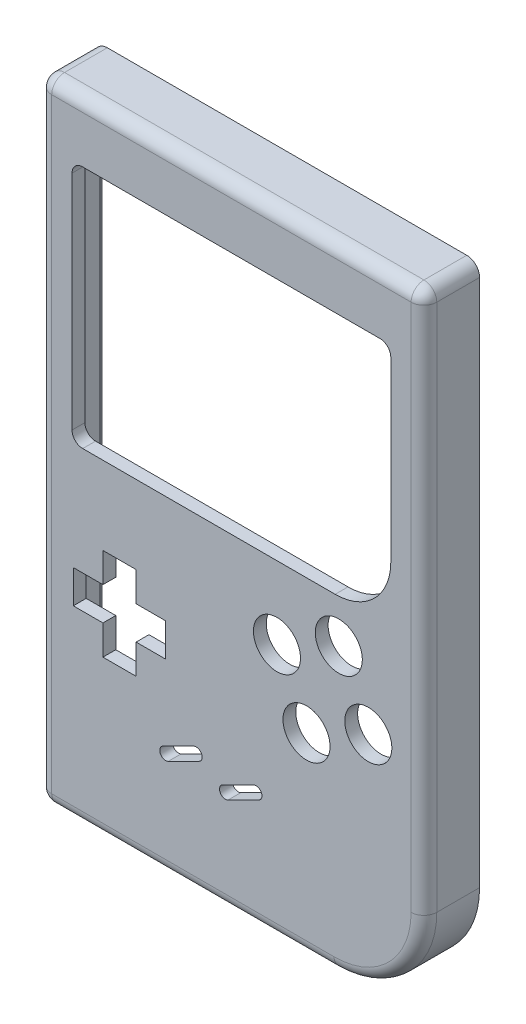
SolidWorks part; units mm, degrees
ref_plane "Front Plane" through (0, 0, 0) normal (0, 0, 1) x (1, 0, 0)
ref_plane "Top Plane" through (0, 0, 0) normal (0, 1, 0) x (1, 0, 0)
ref_plane "Right Plane" through (0, 0, 0) normal (1, 0, 0) x (0, 0, -1)
sketch "Sketch1" plane through (0, 0, 0) normal (0, 0, 1) x (1, 0, 0)
  line L1 (-45, -73.75) -> (45, -73.75)
  line L2 (-45, -73.75) -> (-45, 73.75)
  line L3 (-45, 73.75) -> (45, 73.75)
  line L4 (45, -73.75) -> (45, 73.75)
  line L5 (-45, -73.75) -> (45, 73.75) construction
  line L6 (-45, 73.75) -> (45, -73.75) construction
  point P0 (0, 0)
  dimension "D1" = 90
  dimension "D2" = 147.5
extrude "Boss-Extrude1" add sketch "Sketch1" along normal blind 13
fillet "Rounded Bottom Corner" radius 21 1 edges at (45, -73.75, 6.5)
fillet "Round Edges" radius 3 8 edges at (-10.5, -73.75, 13) (38.8492, -67.5992, 13) (-45, 0, 13) (45, 10.5, 13) (0, 73.75, 13) (-45, -73.75, 6.5) (-45, 73.75, 6.5) (45, 73.75, 6.5)
shell "Shell2" thickness 3 removed face at (-1.784, 1.784, 0)
sketch "Sketch2" plane through (0, 0, 13) normal (0, 0, 1) x (1, 0, 0)
  line L0 (45, 73.75) -> (-45, 73.75) construction
  line L1 (-34.75, 59.75) -> (34.75, 59.75)
  line L2 (-37.25, 57.25) -> (-37.25, 5.25)
  line L3 (-34.75, 2.75) -> (24.25, 2.75)
  line L4 (37.25, 57.25) -> (37.25, 15.75)
  line L6 (0, -7.15) -> (0, 7.15) construction
  arc A0 (-37.25, 5.25) -> (-34.75, 2.75) centre (-34.75, 5.25) ccw
  arc A1 (34.75, 59.75) -> (37.25, 57.25) centre (34.75, 57.25) cw
  arc A2 (-34.75, 59.75) -> (-37.25, 57.25) centre (-34.75, 57.25) ccw
  arc A3 (24.25, 2.75) -> (37.25, 15.75) centre (24.25, 15.75) ccw
  point P8 (0, 59.75)
  dimension "D4" = 2.5
  dimension "D5" = 13
  dimension "D1" = 14
  dimension "D2" = 74.5
  dimension "D3" = 57
extrude "Cut-Extrude1" cut sketch "Sketch2" against normal through all
sketch "Sketch3" plane through (0, 0, 0) normal (0, 0, -1) x (-1, 0, 0)
  line L0 (-42, -52.75) -> (-42, 70.75) construction
  line L1 (-42, 70.75) -> (42, 70.75) construction
  line L2 (42, -70.75) -> (42, 70.75) construction
  line L3 (-24, -70.75) -> (42, -70.75) construction
  line L4 (-42, -52.75) -> (-42, 70.75)
  line L5 (-42, 70.75) -> (42, 70.75)
  line L6 (42, -70.75) -> (42, 70.75)
  line L7 (-24, -70.75) -> (42, -70.75)
  line L8 (-43.25, -52.75) -> (-43.25, 72)
  line L9 (-43.25, 72) -> (43.25, 72)
  line L10 (43.25, -72) -> (43.25, 72)
  line L11 (-24, -72) -> (43.25, -72)
  arc A0 (-42, -52.75) -> (-24, -70.75) centre (-24, -52.75) ccw construction
  arc A1 (-42, -52.75) -> (-24, -70.75) centre (-24, -52.75) ccw
  arc A2 (-43.25, -52.75) -> (-24, -72) centre (-24, -52.75) ccw
  dimension "D1" = 1.25
extrude "Cut-Extrude2" cut sketch "Sketch3" against normal blind 1.75
sketch "Sketch4" plane through (0, -73.75, 0) normal (0, -1, 0) x (1, 0, 0)
  line L0 (-3.5, 0) -> (3.5, 0)
  line L1 (-42, 0) -> (24, 0) construction
  line L2 (-3.5, 0) -> (-3.5, 4)
  line L3 (3.5, 0) -> (3.5, 4)
  arc A0 (-3.5, 4) -> (3.5, 4) centre (0, 4) cw
  point P6 (0, 0)
  dimension "D1" = 7
  dimension "D2" = 4
extrude "Cut-Extrude3" cut sketch "Sketch4" against normal up to next
sketch "Sketch6" plane through (0, 0, 13) normal (0, 0, 1) x (1, 0, 0)
  line L0 (45, 70.75) -> (45, -52.75) construction
  line L1 (24, -73.75) -> (-42, -73.75) construction
  line L2 (17.5469, -28.66) -> (32, -21.75) construction
  line L3 (17.5469, -28.66) -> (10.6455, -14.2249) construction
  line L4 (32, -21.75) -> (25.0986, -7.3149) construction
  line L5 (10.6455, -14.2249) -> (25.0986, -7.3149) construction
  circle A0 centre (32, -21.75) radius 5.5
  circle A1 centre (17.5469, -28.66) radius 5.5
  circle A2 centre (25.0986, -7.3149) radius 5.5
  circle A3 centre (10.6455, -14.2249) radius 5.5
  dimension "D1" = 11
  dimension "D4" = 45.09
  dimension "D6" = 11
  dimension "D8" = 11
  dimension "D9" = 11
  dimension "D2" = 13
  dimension "D3" = 52
  dimension "D5" = 16.02
  dimension "D7" = 16
extrude "Cut-Extrude4" cut sketch "Sketch6" against normal through all
sketch "Sketch7" plane through (0, 0, 13) normal (0, 0, 1) x (1, 0, 0)
  line L0 (-45, -70.75) -> (-45, 70.75) construction
  line L1 (-29.525, -16.01) -> (-22.775, -16.01) construction
  line L2 (-36.45, -22.935) -> (-36.45, -29.685) construction
  line L3 (-29.525, -36.61) -> (-22.775, -36.61) construction
  line L4 (-15.85, -22.935) -> (-15.85, -29.685) construction
  line L5 (24, -73.75) -> (-42, -73.75) construction
  line L6 (-22.775, -16.01) -> (-29.525, -36.61) construction
  line L7 (-29.525, -16.01) -> (-22.775, -16.01)
  line L8 (-29.525, -16.01) -> (-29.525, -36.61) construction
  line L9 (-29.525, -36.61) -> (-22.775, -36.61)
  line L10 (-22.775, -16.01) -> (-22.775, -36.61) construction
  line L11 (-15.85, -29.685) -> (-36.45, -29.685) construction
  line L12 (-15.85, -29.685) -> (-15.85, -22.935)
  line L13 (-15.85, -22.935) -> (-36.45, -22.935) construction
  line L14 (-36.45, -29.685) -> (-36.45, -22.935)
  line L15 (-36.45, -29.685) -> (-15.85, -22.935) construction
  line L16 (-29.525, -16.01) -> (-22.775, -36.61) construction
  line L17 (-15.85, -29.685) -> (-36.45, -22.935) construction
  line L18 (-30.025, -15.51) -> (-22.275, -15.51)
  line L19 (-22.275, -15.51) -> (-22.275, -37.11)
  line L20 (-30.025, -37.11) -> (-22.275, -37.11)
  line L21 (-30.025, -15.51) -> (-30.025, -37.11)
  line L22 (-15.35, -22.435) -> (-36.95, -22.435)
  line L23 (-36.95, -22.435) -> (-36.95, -30.185)
  line L24 (-15.35, -30.185) -> (-36.95, -30.185)
  line L25 (-15.35, -22.435) -> (-15.35, -30.185)
  point P16 (-26.15, -26.31)
  point P17 (-26.15, -26.31)
  dimension "D1" = 8.55
  dimension "D2" = 29.15
  dimension "D3" = 37.14
  dimension "D4" = 6.75
  dimension "D5" = 6.75
  dimension "D6" = 0.5
extrude "Cut-Extrude5" cut sketch "Sketch7" against normal through all contours L22 L19 L18 L21 | L24 L19 L22 L21 | L25 L22 L19 L24 | L19 L24 L21 L20 | L24 L21 L22 L23 region at (-26.15, -18.9725, 13) region at (-26.15, -26.31, 13) region at (-33.4875, -26.31, 13) region at (-18.8125, -26.31, 13) region at (-26.15, -33.6475, 13)
sketch "Sketch8" plane through (0, 0, 13) normal (0, 0, 1) x (1, 0, 0)
  line L0 (-1.4, -50.18) -> (5.7593, -46.61) construction
  line L1 (-2.0136, -48.9495) -> (5.1457, -45.3795)
  line L2 (-0.7864, -51.4105) -> (6.3729, -47.8405)
  line L3 (-15.37, -49.33) -> (-8.2107, -45.76) construction
  line L4 (-15.9836, -48.0995) -> (-8.8243, -44.5295)
  line L5 (-14.7564, -50.5605) -> (-7.5971, -46.9905)
  line L6 (24, -73.75) -> (-42, -73.75) construction
  line L7 (-45, -70.75) -> (-45, 70.75) construction
  arc A0 (-2.0136, -48.9495) -> (-0.7864, -51.4105) centre (-1.4, -50.18) ccw
  arc A1 (6.3729, -47.8405) -> (5.1457, -45.3795) centre (5.7593, -46.61) ccw
  arc A2 (-15.9836, -48.0995) -> (-14.7564, -50.5605) centre (-15.37, -49.33) ccw
  arc A3 (-7.5971, -46.9905) -> (-8.8243, -44.5295) centre (-8.2107, -45.76) ccw
  point P2 (2.1796, -48.395)
  point P7 (-11.7904, -47.545)
  point P14 (0, 0)
  dimension "D1" = 2.75
  dimension "D2" = 23.57
  dimension "D3" = 27.14
  dimension "D4" = 8
  dimension "D5" = 29.63
  dimension "D6" = 13.97
  dimension "D7" = 27.99
extrude "Cut-Extrude6" cut sketch "Sketch8" against normal through all
